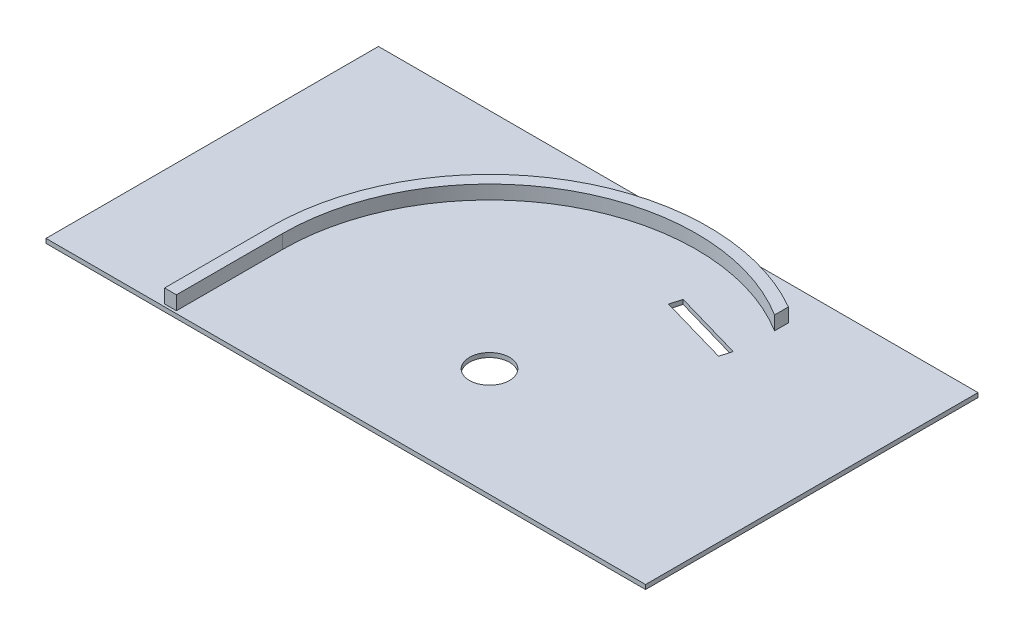
SolidWorks part; units mm, degrees
material "Particle Board"
ref_plane "Front Plane" through (0, 0, 0) normal (0, 0, 1) x (1, 0, 0)
ref_plane "Top Plane" through (0, 0, 0) normal (0, 1, 0) x (1, 0, 0)
ref_plane "Right Plane" through (0, 0, 0) normal (1, 0, 0) x (0, 0, -1)
sketch "Sketch3" plane through (0, 0, 0) normal (0, 1, 0) x (1, 0, 0)
  line L1 (0, 0) -> (-839.8654, 0) construction
  line L2 (0, 0) -> (-451.1992, 260.5) construction
  line L5 (-524, 0) -> (-554, 0)
  line L6 (277.6777, 444.3772) -> (277.6777, 479.3862)
  circle A0 centre (0, 0) radius 254 construction
  arc A3 (277.6777, 444.3772) -> (-524, 0) centre (0, 0) ccw
  arc A4 (277.6777, 479.3862) -> (-554, 0) centre (0, 0) ccw
  arc A5 (293.5753, 469.8186) -> (-554, 0) centre (0, 0) ccw construction
  dimension "D1" = 524
  dimension "D2" = 30
  dimension "D4" = 122
  dimension "D5" = 508
  dimension "D3" = 30
extrude "Boss-Extrude1" add sketch "Sketch3" along normal blind 35
sketch "Sketch4" plane through (0, 0, 0) normal (0, 1, 0) x (1, 0, 0)
  line L0 (-538.2597, 554) -> (609.3192, 554) construction
  line L5 (-848, 566.7) -> (670.6777, 566.7)
  line L6 (-848, 566.7) -> (-848, -275.4)
  line L7 (-848, -275.4) -> (670.6777, -275.4)
  line L8 (670.6777, 566.7) -> (670.6777, -275.4)
  arc A0 (277.6777, 479.3862) -> (-554, 0) centre (0, 0) ccw construction
  dimension "D1" = 275.4
  dimension "D2" = 294
  dimension "D3" = 12.7
  dimension "D4" = 393
extrude "Boss-Extrude2" add sketch "Sketch4" against normal blind 11.1125
hole_wizard "Ø20.0mm Dowel Hole1" positions "Sketch6" profile "Sketch7" hole size "Ø20.0" standard "ANSI Metric" end condition through all
sketch "Sketch6" plane through (0, 0, 0) normal (0, 1, 0) x (1, 0, 0)
  point P0 (0, 0)
sketch "Sketch7" plane through (0, 0, 0) normal (1, 0, 0) x (0, 0, 1)
  line L0 (0, 0) -> (0, 11.1125)
  line L1 (0, 11.1125) -> (50.8, 11.1125)
  line L2 (50.8, 11.1125) -> (50.8, 0)
  line L5 (50.8, 0) -> (0, 0)
  line L11 (0, -6.35) -> (0, 107.95) construction
  dimension "Thru Hole Dia." = 101.6
  dimension "Thru Hole Depth" = 11.1125
ref_plane "Plane1" through (0, 0, 269.05) normal (0, 0, 1) x (1, 0, 0)
sketch "Sketch8" plane through (0, 0, 0) normal (0, 0, 1) x (1, 0, 0)
  line L1 (-554, 35) -> (-524, 35)
  line L2 (-554, 35) -> (-554, 0)
  line L3 (-554, 0) -> (-524, 0)
  line L4 (-524, 35) -> (-524, 0)
extrude "Boss-Extrude3" add sketch "Sketch8" along normal up to surface (269.05 mm away) up to plane "Plane1"
sketch "Sketch9" plane through (0, 0, 0) normal (0, 1, 0) x (1, 0, 0)
  line L0 (270.6777, 346.7) -> (92.8443, 397.6929)
  line L1 (92.8443, 397.6929) -> (84.5752, 368.8551)
  line L2 (84.5752, 368.8551) -> (262.4086, 317.8621)
  line L3 (262.4086, 317.8621) -> (270.6777, 346.7)
  line L4 (670.6777, 566.7) -> (-848, 566.7) construction
  line L5 (670.6777, -275.4) -> (670.6777, 566.7) construction
  dimension "D1" = 185
  dimension "D2" = 30
  dimension "D3" = 16
  dimension "D4" = 400
  dimension "D5" = 220
extrude "Cut-Extrude1" cut sketch "Sketch9" against normal through all
